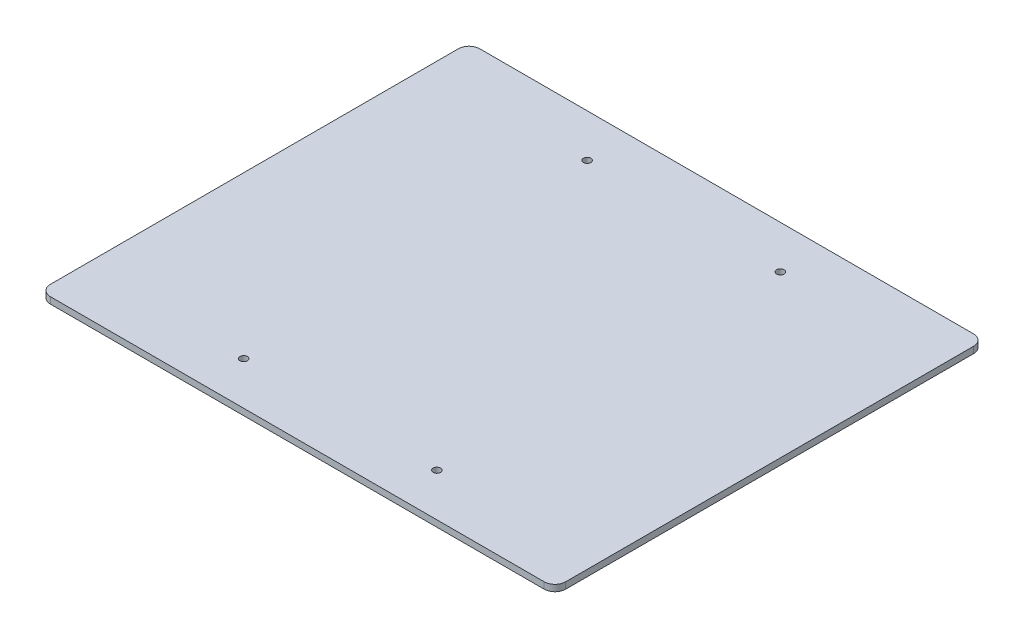
SolidWorks part; units mm, degrees
ref_plane "前视基准面" through (0, 0, 0) normal (0, 0, 1) x (1, 0, 0)
ref_plane "上视基准面" through (0, 0, 0) normal (0, 1, 0) x (1, 0, 0)
ref_plane "右视基准面" through (0, 0, 0) normal (1, 0, 0) x (0, 0, -1)
other "Configuration Table"
sketch "草图1" plane through (0, 0, 0) normal (0, 1, 0) x (1, 0, 0)
  line L1 (-120, -100) -> (120, -100)
  line L2 (-120, -100) -> (-120, 100)
  line L3 (-120, 100) -> (120, 100)
  line L4 (120, -100) -> (120, 100)
  line L5 (-120, -100) -> (120, 100) construction
  line L6 (-120, 100) -> (120, -100) construction
  point P0 (0, 0)
  dimension "D1" = 240
  dimension "D2" = 200
extrude "凸台-拉伸1" add sketch "草图1" along normal blind 3
fillet "圆角1" radius 5 4 edges at (-120, 1.5, 100) (-120, 1.5, -100) (120, 1.5, 100) (120, 1.5, -100)
sketch "草图2" plane through (0, 0, 0) normal (0, -1, 0) x (1, 0, 0)
  line L0 (0, 0) -> (50000, 0) construction
  line L1 (0, 0) -> (0, 50000) construction
  circle A0 centre (-45, 80) radius 1.75
  circle A1 centre (45, 80) radius 1.75
  circle A2 centre (45, -80) radius 1.75
  circle A3 centre (-45, -80) radius 1.75
  dimension "D1" = 3.5
  dimension "D2" = 80
extrude "切除-拉伸1" cut sketch "草图2" against normal blind 18
